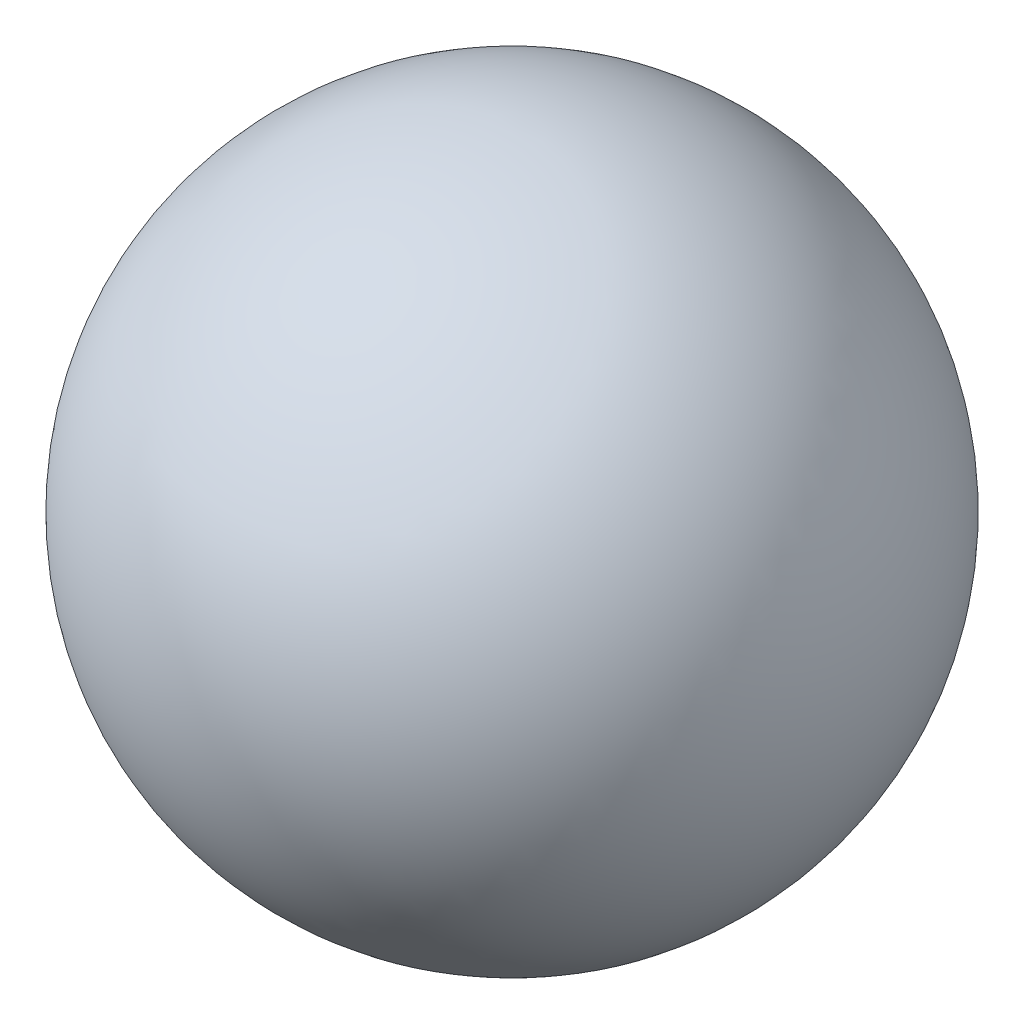
SolidWorks part; units mm, degrees
ref_plane "Front" through (0, 0, 0) normal (0, 0, 1) x (1, 0, 0)
ref_plane "Top" through (0, 0, 0) normal (0, 1, 0) x (1, 0, 0)
ref_plane "Right" through (0, 0, 0) normal (1, 0, 0) x (0, 0, -1)
sketch "Sketch2" plane through (0, 0, 0) normal (1, 0, 0) x (0, 0, -1)
  line L0 (0, -2.25) -> (0, 2.25)
  circle A0 centre (0, 0) radius 2.25 construction
  arc A1 (0, 2.25) -> (0, -2.25) centre (0, 0) cw
  dimension "D1" = 4.5
revolve "Revolve1" add sketch "Sketch2" angle 360 about L0 region at (0, 0, -0.9549)
sketch "Bearing Slot Cut Guide Loose" plane through (0, 0, 0) normal (1, 0, 0) x (0, 0, -1)
  line L0 (-1.35, 2.2) -> (1.35, 2.2)
  line L1 (1.35, 2.2) -> (1.7642, 1.7858)
  line L2 (2.35, 0.3716) -> (2.35, -0.3716)
  line L3 (-1.35, 2.2) -> (-1.7642, 1.7858)
  line L4 (-2.35, 0.3716) -> (-2.35, -0.3716)
  line L5 (0, 0) -> (0, 2.2) construction
  line L6 (0, 0) -> (-2.35, 0) construction
  line L7 (-1.35, -2.2) -> (-1.7642, -1.7858)
  line L8 (-1.35, -2.2) -> (1.35, -2.2)
  line L9 (1.35, -2.2) -> (1.7642, -1.7858)
  arc A0 (1.7642, -1.7858) -> (2.35, -0.3716) centre (0.35, -0.3716) ccw
  arc A1 (-1.7642, -1.7858) -> (-2.35, -0.3716) centre (-0.35, -0.3716) cw
  arc A2 (1.7642, 1.7858) -> (2.35, 0.3716) centre (0.35, 0.3716) cw
  circle A3 centre (0, 0) radius 2.35 construction
  arc A4 (-1.7642, 1.7858) -> (-2.35, 0.3716) centre (-0.35, 0.3716) ccw
  circle A5 centre (0, 0) radius 2.25 construction
  circle A6 centre (0, 0) radius 2.25 construction
  circle A7 centre (0, 0) radius 2.2
  point P5 (0, 2.35)
  point P14 (2.35, 0)
  point P17 (2.35, -1.2)
  point P20 (-2.35, -1.2)
  point P23 (2.35, 1.2)
  point P26 (-2.35, 1.2)
  dimension "D1" = 4.7
  dimension "D5" = 2
  dimension "D2" = 45
  dimension "D3" = 1
  dimension "D4" = 0.05
sketch "Bearing Slot Cut Guide Tight" plane through (0, 0, 0) normal (1, 0, 0) x (0, 0, -1)
  line L0 (-1.35, 2.2) -> (1.35, 2.2) construction
  line L1 (1.35, 2.2) -> (1.7642, 1.7858) construction
  line L2 (2.35, 0.3716) -> (2.35, -0.3716) construction
  line L3 (1.35, -2.2) -> (1.7642, -1.7858) construction
  line L4 (-1.35, -2.2) -> (1.35, -2.2) construction
  line L5 (-1.35, -2.2) -> (-1.7642, -1.7858) construction
  line L6 (-2.35, 0.3716) -> (-2.35, -0.3716) construction
  line L7 (-1.35, 2.2) -> (-1.7642, 1.7858) construction
  line L8 (-1.35, 2.2) -> (1.35, 2.2) construction
  line L9 (1.35, 2.2) -> (1.7642, 1.7858) construction
  line L10 (2.35, 0.3716) -> (2.35, -0.3716)
  line L11 (1.35, -2.2) -> (1.7642, -1.7858)
  line L12 (-1.35, -2.2) -> (1.35, -2.2)
  line L13 (-1.35, -2.2) -> (-1.7642, -1.7858)
  line L14 (-2.35, 0.3716) -> (-2.35, -0.3716)
  line L15 (-1.35, 2.2) -> (-1.7642, 1.7858) construction
  line L16 (-1.7642, 1.7858) -> (-1.375, 2.175)
  line L17 (-1.375, 2.175) -> (1.375, 2.175)
  line L18 (1.375, 2.175) -> (1.7642, 1.7858)
  arc A0 (2.35, 0.3716) -> (1.7642, 1.7858) centre (0.35, 0.3716) ccw construction
  arc A1 (1.7642, -1.7858) -> (2.35, -0.3716) centre (0.35, -0.3716) ccw construction
  arc A2 (-2.35, -0.3716) -> (-1.7642, -1.7858) centre (-0.35, -0.3716) ccw construction
  arc A3 (-1.7642, 1.7858) -> (-2.35, 0.3716) centre (-0.35, 0.3716) ccw construction
  arc A4 (2.35, 0.3716) -> (1.7642, 1.7858) centre (0.35, 0.3716) ccw
  arc A5 (1.7642, -1.7858) -> (2.35, -0.3716) centre (0.35, -0.3716) ccw
  arc A6 (-2.35, -0.3716) -> (-1.7642, -1.7858) centre (-0.35, -0.3716) ccw
  arc A7 (-1.7642, 1.7858) -> (-2.35, 0.3716) centre (-0.35, 0.3716) ccw
  dimension "D1" = 0.05
